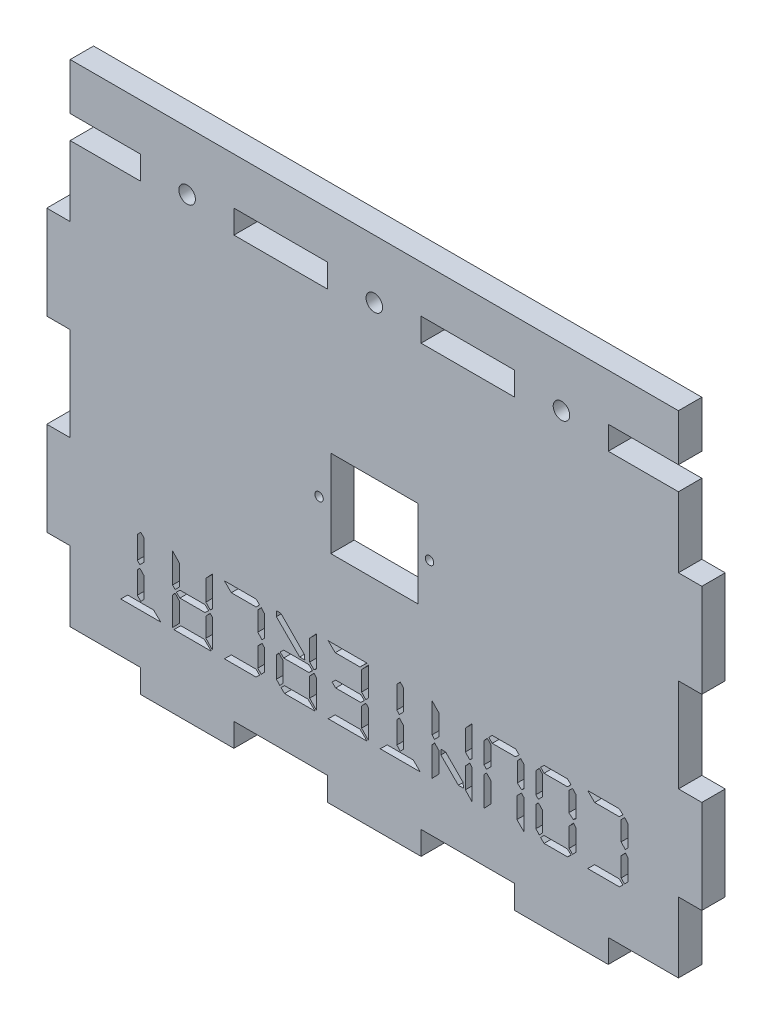
SolidWorks part; units mm, degrees
ref_plane "Front Plane" through (0, 0, 0) normal (0, 0, 1) x (1, 0, 0)
ref_plane "Top Plane" through (0, 0, 0) normal (0, 1, 0) x (1, 0, 0)
ref_plane "Right Plane" through (0, 0, 0) normal (1, 0, 0) x (0, 0, -1)
sketch "Sketch1" plane through (0, 0, 0) normal (0, 0, 1) x (1, 0, 0)
  line L1 (0, 0) -> (177.8, 0)
  line L2 (0, 0) -> (0, 139.7)
  line L3 (0, 139.7) -> (177.8, 139.7)
  line L4 (177.8, 0) -> (177.8, 139.7)
  dimension "D1" = 177.8
  dimension "D2" = 139.7
extrude "Boss-Extrude1" add sketch "Sketch1" along normal blind 6.35
sketch "Sketch5" plane through (0, 0, 6.35) normal (0, 0, 1) x (1, 0, 0)
  line L1 (0, 0) -> (6.35, 0)
  line L2 (0, 0) -> (0, 25.4)
  line L3 (0, 25.4) -> (6.35, 25.4)
  line L4 (6.35, 0) -> (6.35, 25.4)
  dimension "D1" = 25.4
  dimension "D2" = 6.35
extrude "Cut-Extrude4" cut sketch "Sketch5" against normal blind 6.35
sketch "Sketch6" plane through (0, 0, 6.35) normal (0, 0, 1) x (1, 0, 0)
  line L1 (0, 0) -> (25.4, 0)
  line L2 (0, 0) -> (0, 6.35)
  line L3 (0, 6.35) -> (25.4, 6.35)
  line L4 (25.4, 0) -> (25.4, 6.35)
  dimension "D1" = 6.35
  dimension "D2" = 25.4
extrude "Cut-Extrude5" cut sketch "Sketch6" against normal blind 6.35
pattern_linear "LPattern5" count 3 spacing 50.8 along (0, 1, 0) count 2 spacing 171.45 along (1, 0, 0) of "Cut-Extrude4"
pattern_linear "LPattern6" count 4 spacing 50.8 along (1, 0, 0) count 2 spacing 120.65 along (0, 1, 0) of "Cut-Extrude5"
sketch "Sketch7" plane through (0, 0, 6.35) normal (0, 0, 1) x (1, 0, 0)
  line L1 (6.35, 120.65) -> (0, 120.65)
  line L2 (6.35, 120.65) -> (6.35, 139.7)
  line L3 (6.35, 139.7) -> (0, 139.7)
  line L4 (0, 120.65) -> (0, 139.7)
  dimension "D1" = 6.35
  dimension "D2" = 19.05
extrude "Cut-Extrude6" cut sketch "Sketch7" against normal blind 6.35
sketch "Sketch12" plane through (0, 0, 6.35) normal (0, 0, 1) x (1, 0, 0)
  line L0 (177.8, 127) -> (177.8, 139.7) construction
  line L1 (177.8, 139.7) -> (171.45, 139.7)
  line L2 (177.8, 139.7) -> (177.8, 127)
  line L3 (177.8, 127) -> (171.45, 127)
  line L4 (171.45, 139.7) -> (171.45, 127)
  line L5 (177.8, 139.7) -> (6.35, 139.7) construction
  dimension "D1" = 6.35
  dimension "D2" = 12.7
extrude "Cut-Extrude9" cut sketch "Sketch12" against normal blind 7.62
hole_wizard "#8 Clearance Hole1" positions "Sketch10" profile "Sketch9" hole size "#8" standard "ANSI Inch"
sketch "Sketch10" plane through (0, 0, 6.35) normal (0, 0, 1) x (1, 0, 0)
  line L2 (25.4, 120.65) -> (25.4, 127) construction
  line L3 (76.2, 127) -> (50.8, 127) construction
  line L4 (127, 120.65) -> (127, 127) construction
  point P0 (38.1, 123.825)
  point P2 (88.9, 123.825)
  point P10 (25.4, 123.825)
  point P16 (139.7, 123.825)
  dimension "D1" = 12.7
  dimension "D2" = 12.7
  dimension "D3" = 12.7
  dimension "D4" = 3.175
sketch "Sketch9" plane through (38.1, 123.825, 6.35) normal (1, 0, 0) x (0, -1, 0)
  line L0 (0, 0) -> (0, 11.5107)
  line L1 (0, 11.5107) -> (2.2479, 10.16)
  line L2 (2.2479, 10.16) -> (2.2479, 0)
  line L5 (2.2479, 0) -> (0, 0)
  line L10 (0, 11.5107) -> (-2.2479, 10.16) construction
  line L11 (0, -6.35) -> (0, 107.95) construction
  dimension "Hole Dia." = 4.4958
  dimension "Hole Depth" = 10.16
  dimension "Drill Angle" = 118
sketch "Sketch11" plane through (0, 0, 6.35) normal (0, 0, 1) x (1, 0, 0)
  line L1 (77.089, 82.55) -> (100.711, 82.55)
  line L2 (77.089, 82.55) -> (77.089, 58.928)
  line L3 (77.089, 58.928) -> (100.711, 58.928)
  line L4 (100.711, 82.55) -> (100.711, 58.928)
  line L6 (0, 101.6) -> (0, 76.2) construction
  line L7 (50.8, 120.65) -> (76.2, 120.65) construction
  circle A0 centre (73.914, 70.739) radius 1.143
  circle A1 centre (103.886, 70.739) radius 1.143
  point P6 (88.9, 82.55)
  point P13 (100.711, 70.739)
  point P14 (77.089, 70.739)
  dimension "D5" = 2.286
  dimension "D6" = 2.286
  dimension "D7" = 14.986
  dimension "D8" = 14.986
  dimension "D1" = 38.1
  dimension "D2" = 23.622
  dimension "D3" = 23.622
  dimension "D4" = 88.9
extrude "Cut-Extrude8" cut sketch "Sketch11" against normal blind 7.62
sketch "Sketch13" plane through (0, 0, 6.35) normal (0, 0, 1) x (1, 0, 0)
  line L0 (0, 38.1) -> (177.8, 38.1)
  line L4 (171.45, 139.7) -> (6.35, 139.7) construction
  dimension "D1" = 177.8
  dimension "D2" = 101.6
sketch "Sketch14" plane through (0, 0, 6.35) normal (0, 0, 1) x (1, 0, 0)
  text T0 "CounterCat" font "DS-Digital" height in points 72
extrude "Cut-Extrude10" cut sketch "Sketch14" against normal blind 10.16
